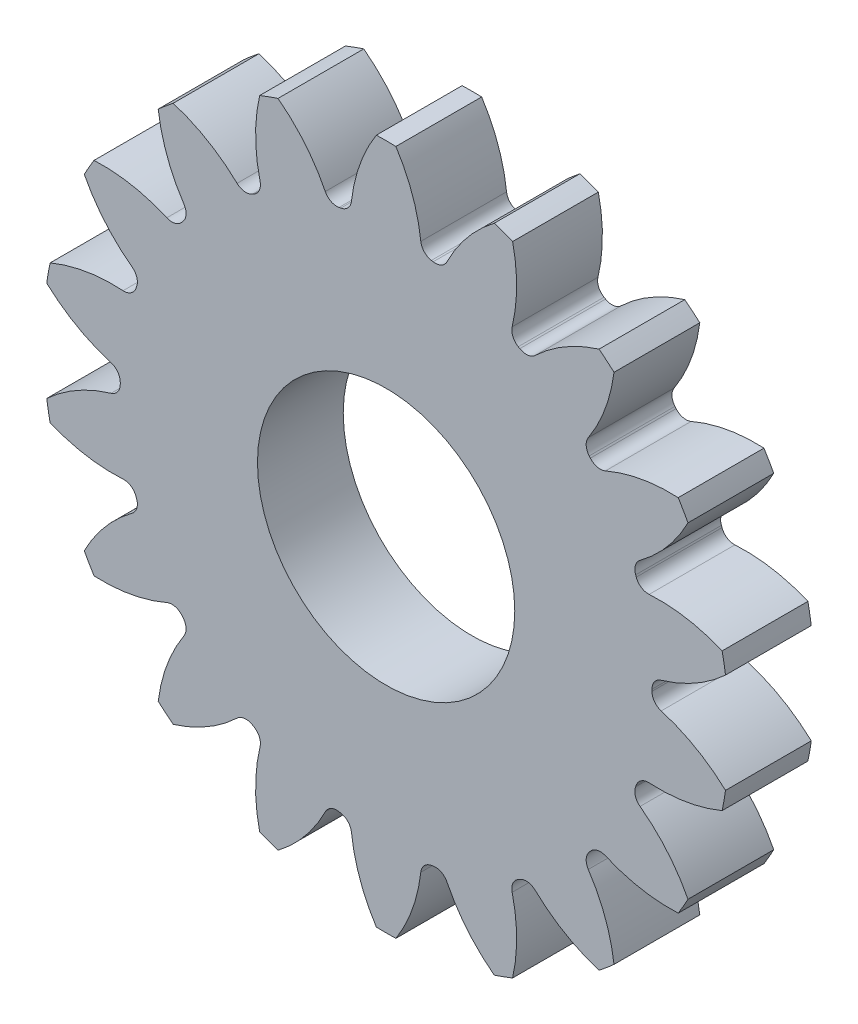
SolidWorks part; units mm, degrees
ref_plane "정면" through (0, 0, 0) normal (0, 0, 1) x (1, 0, 0)
ref_plane "윗면" through (0, 0, 0) normal (0, 1, 0) x (1, 0, 0)
ref_plane "우측면" through (0, 0, 0) normal (1, 0, 0) x (0, 0, -1)
sketch "스케치1" plane through (0, 0, 0) normal (0, 0, 1) x (1, 0, 0)
  line L0 (0, 23.3301) -> (0, -28.0899) construction
  line L1 (-1.57, 17.9314) -> (-1.57, -28.0899) construction
  line L2 (-2.07, 15.3612) -> (-2.07, -28.0899) construction
  line L3 (-0.57, 19.9919) -> (-0.57, -28.0899) construction
  line L4 (-2.07, 23.3301) -> (-2.07, -28.0899) construction
  line L5 (-1.57, 23.3301) -> (-1.57, -28.0899) construction
  line L6 (-0.57, 23.3301) -> (-0.57, -28.0899) construction
  circle A0 centre (0, 0) radius 15.5
  circle A1 centre (0, 0) radius 20
  circle A2 centre (0, 0) radius 18 construction
  arc A3 (-2.07, 15.3612) -> (-0.57, 19.9919) centre (7.394, 14.8538) cw
  arc A4 (2.07, 15.3612) -> (0.57, 19.9919) centre (-7.394, 14.8538) ccw
  dimension "D1" = 31
  dimension "D2" = 36
  dimension "D3" = 40
  dimension "D4" = 1.57
  dimension "D5" = 0.5
  dimension "D6" = 1
extrude "보스-돌출1" add sketch "스케치1" along normal blind 5 contours A0 region at (0, 0, 0)
extrude "보스-돌출2" add sketch "스케치1<3>" along normal blind 5 contours A0 A1 region at (0, 17.3605, 0)
sketch "스케치1<3>" plane through (0, 0, 0) normal (0, 0, 1) x (1, 0, 0) same geometry as "스케치1"
sketch "스케치2" plane through (0, 0, 5) normal (0, 0, 1) x (1, 0, 0)
  circle A0 centre (0, 0) radius 7.5
  dimension "D1" = 15
extrude "컷-돌출1" cut sketch "스케치2" against normal up to next
fillet "필렛1" radius 0.75 2 edges at (2.07, 15.3612, 2.5) (-2.07, 15.3612, 2.5)
pattern_circular "원형 패턴2" count 18 over 360 about axis through (0, 0, -0.001) along (0, 0, 1) of "필렛1", "보스-돌출2" reverse direction yes
